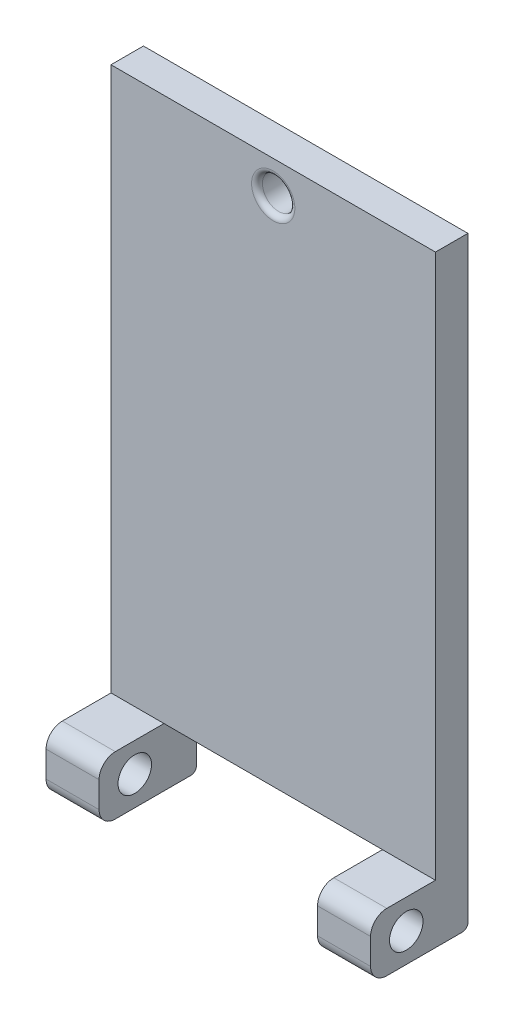
SolidWorks part; units mm, degrees
ref_plane "Front Plane" through (0, 0, 0) normal (0, 0, 1) x (1, 0, 0)
ref_plane "Top Plane" through (0, 0, 0) normal (0, 1, 0) x (1, 0, 0)
ref_plane "Right Plane" through (0, 0, 0) normal (1, 0, 0) x (0, 0, -1)
sketch "Sketch1" plane through (0, 0, 0) normal (0, 0, 1) x (1, 0, 0)
  line L1 (-15, -27.85) -> (15, -27.85)
  line L2 (-15, -27.85) -> (-15, 27.85)
  line L3 (-15, 27.85) -> (15, 27.85)
  line L4 (15, -27.85) -> (15, 27.85)
  line L5 (-15, -27.85) -> (15, 27.85) construction
  line L6 (-15, 27.85) -> (15, -27.85) construction
  point P0 (0, 0)
  dimension "D1" = 55.7
  dimension "D2" = 30
extrude "Boss-Extrude1" add sketch "Sketch1" along normal blind 3
sketch "Sketch2" plane through (0, 0, 3) normal (0, 0, 1) x (1, 0, 0)
  line L0 (0, -27.85) -> (0, 27.85) construction
  line L1 (15, 27.85) -> (-15, 27.85) construction
  line L3 (-15, -27.85) -> (-10.1, -27.85)
  line L4 (-15, -27.85) -> (-15, -22.45)
  line L5 (-15, -22.45) -> (-10.1, -22.45)
  line L6 (-10.1, -27.85) -> (-10.1, -22.45)
  point P6 (0, 0)
  dimension "D1" = 4.9
  dimension "D2" = 5.4
extrude "Boss-Extrude2" add sketch "Sketch2" along normal blind 6
sketch "Sketch3" plane through (-15, 0, 0) normal (-1, 0, 0) x (0, 0, 1)
  line L0 (9, -27.85) -> (0, -27.85) construction
  line L2 (3, 27.85) -> (3, -22.45) construction
  circle A0 centre (5.7, -25.15) radius 1.55
  dimension "D1" = 3.1
  dimension "D2" = 2.7
  dimension "D3" = 2.7
extrude "Cut-Extrude1" cut sketch "Sketch3" against normal through all
mirror "Mirror1" about plane through (0, 0, 0) normal (1, 0, 0) of "Cut-Extrude1", "Boss-Extrude2"
sketch "Sketch4" plane through (0, 0, 3) normal (0, 0, 1) x (1, 0, 0)
  line L1 (15, 27.85) -> (-15, 27.85) construction
  line L3 (0, 27.85) -> (0, 24.85) construction
  circle A0 centre (0, 24.85) radius 1.5
  point P5 (0, 27.35)
  point P6 (0, 27.85)
  dimension "D1" = 3
  dimension "D2" = 3
extrude "Cut-Extrude2" cut sketch "Sketch4" against normal blind 10 contours A0
fillet "Fillet3" radius 0.5 2 edges at (-1.5, 24.85, 0) (1.5, 24.85, 3)
fillet "Fillet4" radius 0.5 2 edges at (0, -27.85, 0) (0, -27.85, 3)
sketch "Sketch5" plane through (0, 0, 3) normal (0, 0, 1) x (1, 0, 0)
  line L0 (10.1, -27.35) -> (10.1, -22.45) construction
  line L1 (-10.1, -27.35) -> (-10.1, -22.45) construction
  line L2 (10.1, -27.35) -> (10.1, -22.45)
  line L3 (-10.1, -27.35) -> (-10.1, -22.45)
  line L4 (-10.1, -22.45) -> (10.1, -22.45)
  line L5 (10.1, -27.35) -> (10.1, -30.3306)
  line L6 (10.1, -30.3306) -> (-10.1, -30.3306)
  line L7 (-10.1, -30.3306) -> (-10.1, -27.35)
  line M2 (-10.1, -22.45) -> (-10.1, -27.35)
  line M3 (-10.1, -27.35) -> (10.1, -27.35)
  line M4 (10.1, -27.35) -> (10.1, -22.45)
extrude "Cut-Extrude4" cut sketch "Sketch5" against normal blind 10 and the other way through all contours L4 M2 M3 M4 | L7 L6 L5 M3 region at (0, -24.9, 3) region at (0, -28.8403, 3)
fillet "Fillet5" radius 1.5 4 edges at (12.55, -27.85, 9) (12.55, -22.45, 9) (-12.55, -27.85, 9) (-12.55, -22.45, 9)
